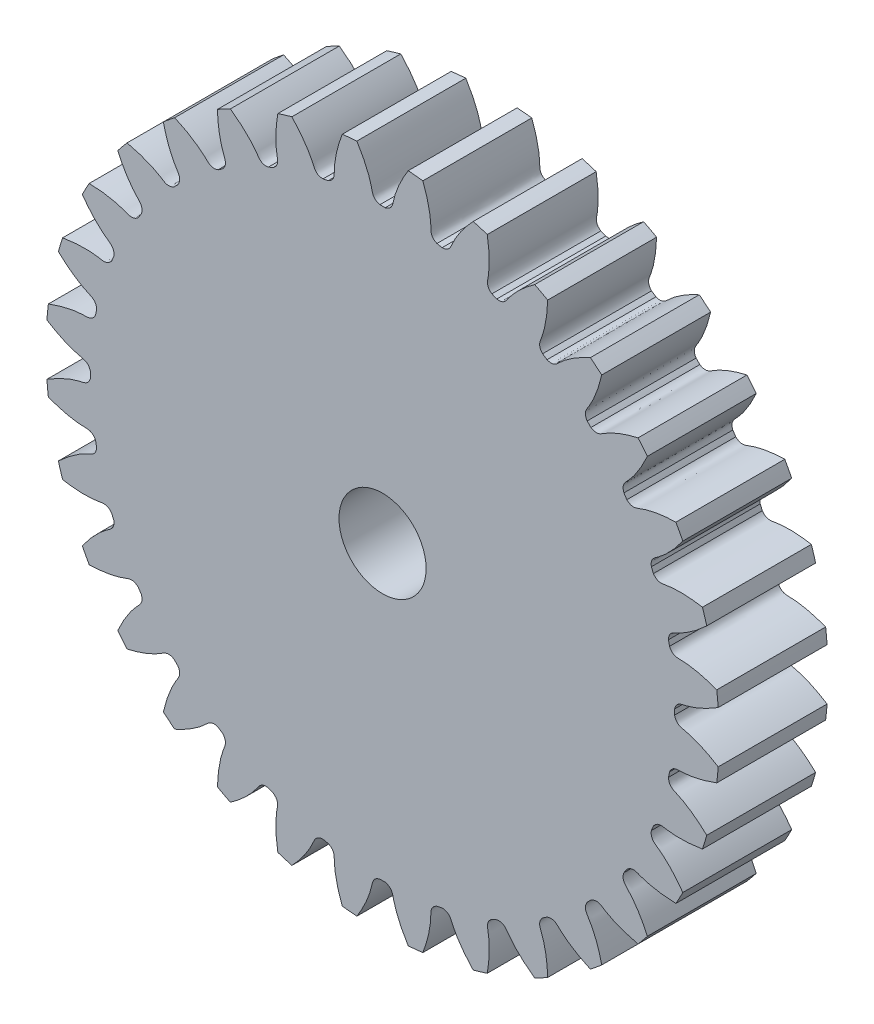
SolidWorks part; units mm, degrees
ref_plane "前视基准面" through (0, 0, 0) normal (0, 0, 1) x (1, 0, 0)
ref_plane "上视基准面" through (0, 0, 0) normal (0, 1, 0) x (1, 0, 0)
ref_plane "右视基准面" through (0, 0, 0) normal (1, 0, 0) x (0, 0, -1)
other "Configuration Table"
sketch "草图1" plane through (0, 0, 0) normal (0, 0, 1) x (1, 0, 0)
  circle A0 centre (0, 0) radius 8.5
extrude "凸台-拉伸1" add sketch "草图1" along normal blind 2.75
ref_axis "基准轴1" through (0, 0, 2.75) along (0, 0, -1)
sketch "草图2" plane through (0, 0, 0) normal (0, 0, 1) x (1, 0, 0)
  line L0 (0, 0) -> (0, 8.5) construction
  circle A0 centre (0, 0) radius 8.5 construction
  arc A1 (0.067, 7.3747) -> (-0.067, 7.3747) centre (0, 0) ccw
  arc A2 (1.6765, 9.6348) -> (-1.6765, 9.6348) centre (0, 0) ccw
  spline S0 degree 3 poles (0.067, 7.3747) (0.2444, 7.4176) (0.2542, 7.5462) (0.2867, 7.6804) (0.2952, 7.7127) (0.3051, 7.7477) (0.3166, 7.7854) (0.3299, 7.8257) (0.3449, 7.8686) (0.3618, 7.9139) (0.3807, 7.9618) (0.4017, 8.012) (0.4249, 8.0645) (0.4505, 8.1193) (0.4785, 8.1763) (0.509, 8.2353) (0.5421, 8.2964) (0.5779, 8.3594) (0.6164, 8.4243) (0.6579, 8.491) (0.7023, 8.5593) (0.7498, 8.6292) (0.8004, 8.7006) (0.8542, 8.7734) (0.9113, 8.8475) (0.9717, 8.9228) (1.0356, 8.9992) (1.1029, 9.0765) (1.1738, 9.1547) (1.2483, 9.2337) (1.3265, 9.3133) (1.4084, 9.3934) (1.5241, 9.5022) (1.6145, 9.5821) (1.6765, 9.6348) knots 0 0 0 0 0.124533 0.135329 0.147193 0.160126 0.174128 0.189198 0.205337 0.222544 0.24082 0.260164 0.280577 0.302059 0.324609 0.348227 0.372914 0.39867 0.425494 0.453386 0.482348 0.512377 0.543476 0.575642 0.608878 0.643181 0.678554 0.714995 0.752504 0.791082 0.830729 0.871444 0.913227 1 1 1 1
  spline S1 degree 3 poles (-0.067, 7.3747) (-0.2444, 7.4176) (-0.2542, 7.5462) (-0.2867, 7.6804) (-0.2952, 7.7127) (-0.3051, 7.7477) (-0.3166, 7.7854) (-0.3299, 7.8257) (-0.3449, 7.8686) (-0.3618, 7.9139) (-0.3807, 7.9618) (-0.4017, 8.012) (-0.4249, 8.0645) (-0.4505, 8.1193) (-0.4785, 8.1763) (-0.509, 8.2353) (-0.5421, 8.2964) (-0.5779, 8.3594) (-0.6164, 8.4243) (-0.6579, 8.491) (-0.7023, 8.5593) (-0.7498, 8.6292) (-0.8004, 8.7006) (-0.8542, 8.7734) (-0.9113, 8.8475) (-0.9717, 8.9228) (-1.0356, 8.9992) (-1.1029, 9.0765) (-1.1738, 9.1547) (-1.2483, 9.2337) (-1.3265, 9.3133) (-1.4084, 9.3934) (-1.5241, 9.5022) (-1.6145, 9.5821) (-1.6765, 9.6348) knots 0 0 0 0 0.124533 0.135329 0.147193 0.160126 0.174128 0.189198 0.205337 0.222544 0.24082 0.260164 0.280577 0.302059 0.324609 0.348227 0.372914 0.39867 0.425494 0.453386 0.482348 0.512377 0.543476 0.575642 0.608878 0.643181 0.678554 0.714995 0.752504 0.791082 0.830729 0.871444 0.913227 1 1 1 1
extrude "切除-拉伸1" cut sketch "草图2" along normal through all
pattern_circular "阵列(圆周)1" count 32 every 11.25 about axis through (0, 0, 2.75) along (0, 0, -1) of "切除-拉伸1"
sketch "草图3" plane through (0, 0, 0) normal (0, 0, 1) x (1, 0, 0)
  circle A0 centre (0, 0) radius 8 construction
  dimension "Dn" = 16
sketch "草图4" plane through (0, 0, 0) normal (0, 0, -1) x (-1, 0, 0)
  circle A0 centre (0, 0) radius 1.1
  dimension "D1" = 2.2
extrude "切除-拉伸2" cut sketch "草图4" against normal up to next
